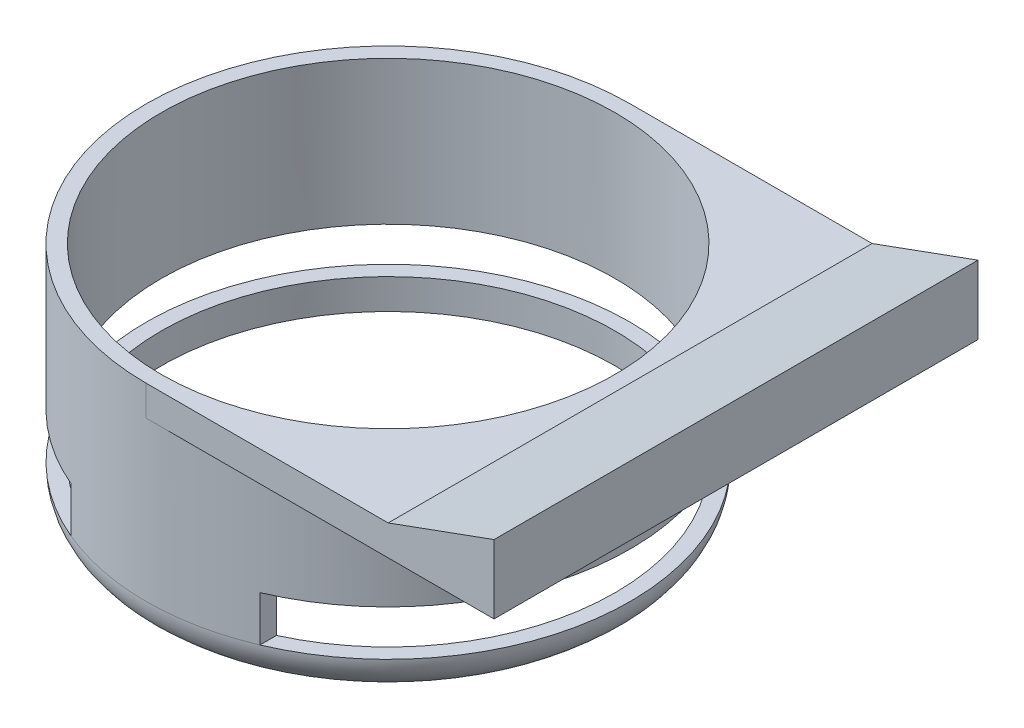
SolidWorks part; units mm, degrees
ref_plane "Front Plane" through (0, 0, 0) normal (0, 0, 1) x (1, 0, 0)
ref_plane "Top Plane" through (0, 0, 0) normal (0, 1, 0) x (1, 0, 0)
ref_plane "Right Plane" through (0, 0, 0) normal (1, 0, 0) x (0, 0, -1)
sketch "Sketch1" plane through (0, 0, 0) normal (0, 1, 0) x (1, 0, 0)
  circle A0 centre (0, 0) radius 40.64
  dimension "D1" = 81.28
extrude "Boss-Extrude1" add sketch "Sketch1" along normal blind 38.1
fillet "Fillet1" radius 6.35 1 edges at (0, 0, 40.64)
sketch "Sketch2" plane through (0, 38.1, 0) normal (0, 1, 0) x (1, 0, 0)
  circle A0 centre (0, 0) radius 38.1
  dimension "D1" = 76.2
extrude "Cut-Extrude1" cut sketch "Sketch2" against normal through all
ref_plane "Plane1" through (0, 0, 0) normal (-0.7071, 0, 0.7071) x (0.7071, 0, 0.7071)
ref_plane "Plane2" through (-28.7368, 0, 28.7368) normal (-0.7071, 0, 0.7071) x (0.7071, 0, 0.7071)
sketch "Sketch12" plane through (0, 38.1, 0) normal (0, 1, 0) x (1, 0, 0)
  line L1 (0, -40.64) -> (58.42, -40.64)
  line L3 (0, 40.64) -> (58.42, 40.64)
  line L4 (58.42, -40.64) -> (58.42, 40.64)
  circle A0 centre (0, 0) radius 40.64 construction
  arc A1 (0, -40.64) -> (0, 40.64) centre (0, 0) ccw
  dimension "D1" = 58.42
  dimension "D2" = 81.28
extrude "Boss-Extrude2" add sketch "Sketch12" against normal blind 5.08 separate body
sketch "Sketch13" plane through (0, 38.1, 0) normal (0, 1, 0) x (1, 0, 0)
  line L1 (58.42, 40.64) -> (40.64, 40.64)
  line L2 (58.42, 40.64) -> (58.42, 0)
  line L4 (40.64, 40.64) -> (40.64, 0)
  line L5 (58.42, -40.64) -> (40.64, -40.64)
  line L6 (58.42, -40.64) -> (58.42, 0)
  line L8 (40.64, -40.64) -> (40.64, 0)
  arc A0 (0, -40.64) -> (0, 40.64) centre (0, 0) ccw construction
extrude "Boss-Extrude3" add sketch "Sketch13" along normal blind 6.4714
sketch "Sketch14" plane through (0, 0, 40.64) normal (0, 0, 1) x (1, 0, 0)
  line L0 (40.64, 38.1) -> (58.42, 44.5714)
  line L1 (40.64, 38.1) -> (40.64, 44.5714)
  line L2 (40.64, 44.5714) -> (58.42, 44.5714)
  line L3 (40.64, 38.1) -> (58.42, 38.1) construction
  line L4 (58.42, 33.02) -> (58.42, 44.5714) construction
extrude "Cut-Extrude4" cut sketch "Sketch14" against normal through all both and the other way through all
sketch "Sketch16" plane through (0, 0, 0) normal (1, 0, 0) x (0, 0, -1)
  line L0 (-40.64, 33.02) -> (-40.64, 6.35) construction
  line L1 (-40.64, 13.97) -> (40.64, 13.97)
  line L2 (-40.64, 13.97) -> (-40.64, 6.35)
  line L3 (-40.64, 6.35) -> (40.64, 6.35)
  line L4 (40.64, 13.97) -> (40.64, 6.35)
  line L5 (40.64, 6.35) -> (40.64, 33.02) construction
  dimension "D1" = 7.62
extrude "Cut-Extrude6" cut sketch "Sketch16" against normal through all both and the other way through all
sketch "Sketch17" plane through (0, 6.35, 0) normal (0, 1, 0) x (1, 0, 0)
  line L0 (15.875, -34.6352) -> (-15.875, -34.6352) construction
  line L1 (-15.875, -34.6352) -> (-15.875, -37.4111)
  line L2 (15.875, -34.6352) -> (15.875, -37.4111)
  arc A0 (-15.875, -34.6352) -> (15.875, -34.6352) centre (0, 0) ccw
  arc A1 (-15.875, -37.4111) -> (15.875, -37.4111) centre (0, 0) ccw
  dimension "D2" = 38.1
  dimension "D3" = 40.64
  dimension "D1" = 31.75
extrude "Boss-Extrude4" add sketch "Sketch17" along normal blind 7.62
